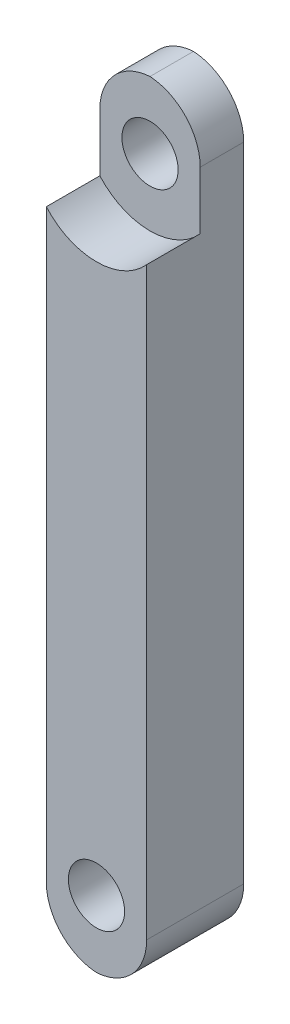
SolidWorks part; units mm, degrees
material "PVC Rigid"
ref_plane "Front Plane" through (0, 0, 0) normal (0, 0, 1) x (1, 0, 0)
ref_plane "Top Plane" through (0, 0, 0) normal (0, 1, 0) x (1, 0, 0)
ref_plane "Right Plane" through (0, 0, 0) normal (1, 0, 0) x (0, 0, -1)
sketch "Sketch1" plane through (0, 0, 0) normal (0, 0, 1) x (1, 0, 0)
  line L1 (-4.7625, 35.56) -> (4.7625, 35.56)
  line L2 (-4.7625, 35.56) -> (-4.7625, -35.56)
  line L3 (-4.7625, -35.56) -> (4.7625, -35.56)
  line L4 (4.7625, 35.56) -> (4.7625, -35.56)
  line L5 (-4.7625, 35.56) -> (4.7625, -35.56) construction
  line L6 (-4.7625, -35.56) -> (4.7625, 35.56) construction
  circle A0 centre (0, -29.21) radius 2.667
  circle A1 centre (0, 29.21) radius 2.667
  point P0 (0, 0)
  dimension "D3" = 5.334
  dimension "D1" = 71.12
  dimension "D2" = 9.525
  dimension "D4" = 6.35
  dimension "D5" = 6.35
extrude "Boss-Extrude1" add sketch "Sketch1" along normal blind 9.2075
fillet "Fillet1" radius 5.08 4 edges at (-4.7625, -35.56, 4.6037) (4.7625, -35.56, 4.6037) (4.7625, 35.56, 4.6037) (-4.7625, 35.56, 4.6037)
sketch "Sketch2" plane through (0, 0, 9.2075) normal (0, 0, 1) x (1, 0, 0)
  circle A0 centre (0, 29.21) radius 6.35
  dimension "D1" = 12.7
extrude "Cut-Extrude1" cut sketch "Sketch2" against normal blind 5.08
